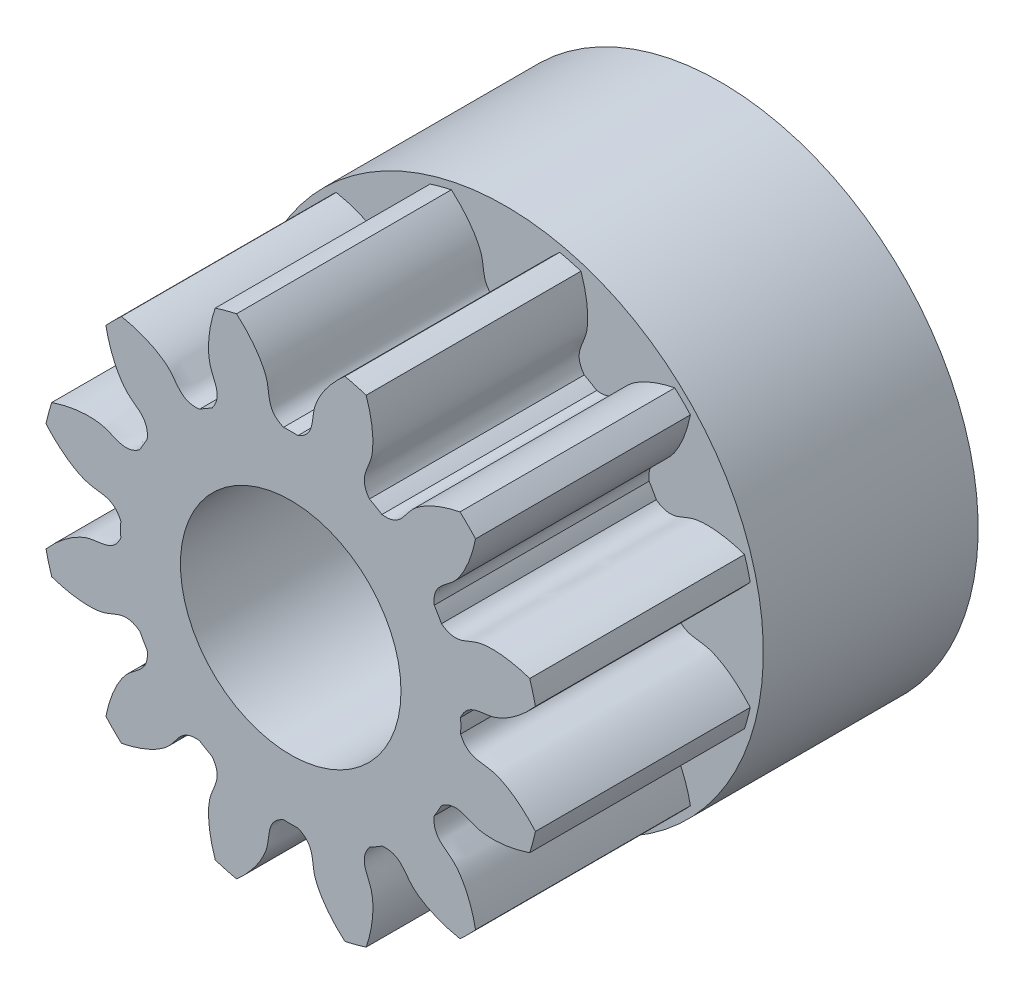
SolidWorks part; units mm, degrees
ref_plane "前视基准面" through (0, 0, 0) normal (0, 0, 1) x (1, 0, 0)
ref_plane "上视基准面" through (0, 0, 0) normal (0, 1, 0) x (1, 0, 0)
ref_plane "右视基准面" through (0, 0, 0) normal (1, 0, 0) x (0, 0, -1)
other "Configuration Table"
sketch "草图1" plane through (0, 0, 0) normal (0, 0, 1) x (1, 0, 0)
  circle A0 centre (0, 0) radius 3.5
extrude "凸台-拉伸1" add sketch "草图1" along normal blind 3
ref_axis "基准轴1" through (0, 0, 3) along (0, 0, -1)
sketch "草图2" plane through (0, 0, 0) normal (0, 0, 1) x (1, 0, 0)
  line L0 (0, 0) -> (0, 3.5) construction
  circle A0 centre (0, 0) radius 3.5 construction
  arc A1 (0.1004, 2.3729) -> (-0.1004, 2.3729) centre (0, 0) ccw
  arc A2 (1.7488, 3.9475) -> (-1.7488, 3.9475) centre (0, 0) ccw
  spline S0 degree 3 poles (0.1004, 2.3729) (0.3404, 2.4747) (0.2872, 2.6724) (0.3381, 2.8447) (0.3413, 2.855) (0.3451, 2.8662) (0.3495, 2.8784) (0.3546, 2.8915) (0.3603, 2.9056) (0.3668, 2.9206) (0.374, 2.9366) (0.3821, 2.9533) (0.3909, 2.971) (0.4007, 2.9894) (0.4114, 3.0086) (0.423, 3.0286) (0.4356, 3.0493) (0.4492, 3.0707) (0.4639, 3.0928) (0.4796, 3.1155) (0.4965, 3.1388) (0.5145, 3.1626) (0.5337, 3.187) (0.554, 3.2119) (0.5756, 3.2372) (0.5985, 3.2629) (0.6226, 3.289) (0.648, 3.3154) (0.6748, 3.342) (0.7028, 3.369) (0.7323, 3.3961) (0.7631, 3.4234) (0.7954, 3.4507) (0.829, 3.4782) (0.8641, 3.5057) (0.9006, 3.5331) (0.9385, 3.5604) (0.978, 3.5877) (1.0189, 3.6147) (1.0613, 3.6416) (1.1052, 3.6681) (1.1506, 3.6944) (1.1975, 3.7203) (1.2459, 3.7457) (1.2958, 3.7707) (1.3472, 3.7952) (1.4001, 3.8191) (1.4546, 3.8424) (1.5105, 3.865) (1.5679, 3.8869) (1.6472, 3.9154) (1.7078, 3.9351) (1.7488, 3.9475) knots 0 0 0 0 0.218015 0.222044 0.226546 0.231522 0.236972 0.242897 0.249295 0.256167 0.263513 0.271332 0.279626 0.288394 0.297636 0.307351 0.317541 0.328204 0.339341 0.350953 0.363038 0.375597 0.38863 0.402137 0.416118 0.430573 0.445502 0.460904 0.476781 0.493132 0.509956 0.527255 0.545027 0.563273 0.581994 0.601188 0.620856 0.640998 0.661614 0.682704 0.704268 0.726305 0.748817 0.771803 0.795262 0.819196 0.843603 0.868484 0.89384 0.919669 0.945972 1 1 1 1
  spline S1 degree 3 poles (-0.1004, 2.3729) (-0.3404, 2.4747) (-0.2872, 2.6724) (-0.3381, 2.8447) (-0.3413, 2.855) (-0.3451, 2.8662) (-0.3495, 2.8784) (-0.3546, 2.8915) (-0.3603, 2.9056) (-0.3668, 2.9206) (-0.374, 2.9366) (-0.3821, 2.9533) (-0.3909, 2.971) (-0.4007, 2.9894) (-0.4114, 3.0086) (-0.423, 3.0286) (-0.4356, 3.0493) (-0.4492, 3.0707) (-0.4639, 3.0928) (-0.4796, 3.1155) (-0.4965, 3.1388) (-0.5145, 3.1626) (-0.5337, 3.187) (-0.554, 3.2119) (-0.5756, 3.2372) (-0.5985, 3.2629) (-0.6226, 3.289) (-0.648, 3.3154) (-0.6748, 3.342) (-0.7028, 3.369) (-0.7323, 3.3961) (-0.7631, 3.4234) (-0.7954, 3.4507) (-0.829, 3.4782) (-0.8641, 3.5057) (-0.9006, 3.5331) (-0.9385, 3.5604) (-0.978, 3.5877) (-1.0189, 3.6147) (-1.0613, 3.6416) (-1.1052, 3.6681) (-1.1506, 3.6944) (-1.1975, 3.7203) (-1.2459, 3.7457) (-1.2958, 3.7707) (-1.3472, 3.7952) (-1.4001, 3.8191) (-1.4546, 3.8424) (-1.5105, 3.865) (-1.5679, 3.8869) (-1.6472, 3.9154) (-1.7078, 3.9351) (-1.7488, 3.9475) knots 0 0 0 0 0.218015 0.222044 0.226546 0.231522 0.236972 0.242897 0.249295 0.256167 0.263513 0.271332 0.279626 0.288394 0.297636 0.307351 0.317541 0.328204 0.339341 0.350953 0.363038 0.375597 0.38863 0.402137 0.416118 0.430573 0.445502 0.460904 0.476781 0.493132 0.509956 0.527255 0.545027 0.563273 0.581994 0.601188 0.620856 0.640998 0.661614 0.682704 0.704268 0.726305 0.748817 0.771803 0.795262 0.819196 0.843603 0.868484 0.89384 0.919669 0.945972 1 1 1 1
extrude "切除-拉伸1" cut sketch "草图2" along normal through all
pattern_circular "阵列(圆周)1" count 12 over 360 about axis through (0, 0, 3) along (0, 0, -1) of "切除-拉伸1"
sketch "草图3" plane through (0, 0, 0) normal (0, 0, 1) x (1, 0, 0)
  circle A0 centre (0, 0) radius 3 construction
  dimension "Dn" = 6
sketch "草图5" plane through (0, 0, 0) normal (0, 0, -1) x (-1, 0, 0)
  circle A0 centre (0, 0) radius 3.6
  dimension "D1" = 7.2
extrude "凸台-拉伸2" add sketch "草图5" along normal blind 3
sketch "草图4" plane through (0, 0, 3) normal (0, 0, 1) x (1, 0, 0)
  circle A0 centre (0, 0) radius 1.54
  dimension "D1" = 3.08
extrude "切除-拉伸2" cut sketch "草图4" against normal up to next
sketch "草图6" plane through (0, 0, 0) normal (0, 1, 0) x (1, 0, 0)
  line L0 (1.54, 3) -> (-1.54, 3) construction
  circle A0 centre (0, 1) radius 0.825
  dimension "D1" = 1.65
  dimension "D2" = 2
extrude "切除-拉伸3" cut sketch "草图6" against normal up to next
